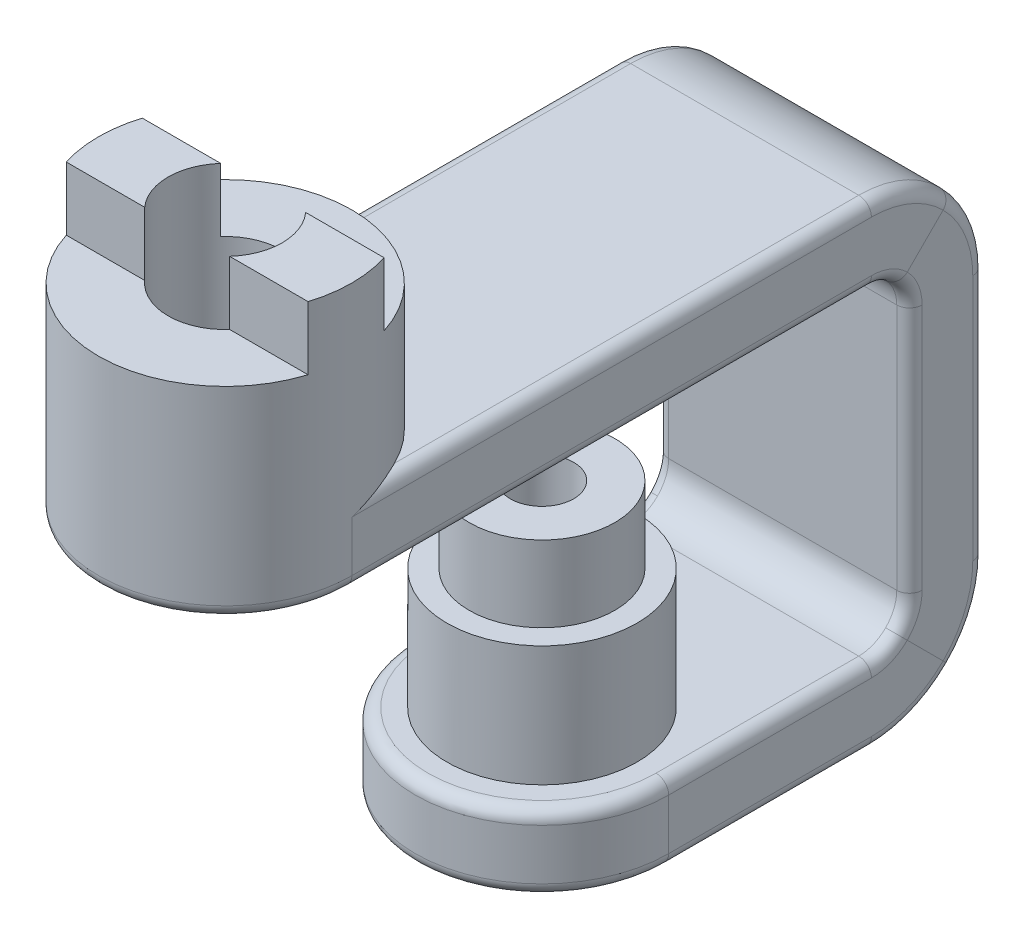
SolidWorks part; units mm, degrees
ref_plane "Front Plane" through (0, 0, 0) normal (0, 0, 1) x (1, 0, 0)
ref_plane "Top Plane" through (0, 0, 0) normal (0, 1, 0) x (1, 0, 0)
ref_plane "Right Plane" through (0, 0, 0) normal (1, 0, 0) x (0, 0, -1)
sketch "Sketch2" plane through (0, 0, 0) normal (1, 0, 0) x (0, 0, -1)
  line L0 (0, 0) -> (50, 0)
  line L1 (50, 0) -> (50, 75)
  line L2 (50, 75) -> (-50, 75)
  dimension "D1" = 75
  dimension "D2" = 50
  dimension "D3" = 100
sketch "Sketch3" plane through (0, 0, 0) normal (0, 0, 1) x (1, 0, 0)
  line L1 (-20, 12) -> (20, 12)
  line L2 (-20, 12) -> (-20, 0)
  line L3 (-20, 0) -> (20, 0)
  line L4 (20, 12) -> (20, 0)
  point P4 (0, 0)
  dimension "D1" = 12
  dimension "D2" = 40
sweep "Sweep1" add profiles "Sketch3" path "Sketch2"
sketch "Sketch4" plane through (0, 12, 0) normal (0, 1, 0) x (1, 0, 0)
  line L0 (20, 0) -> (-20, 0) construction
  line L1 (-20, 0) -> (20, 0)
  arc A0 (-20, 0) -> (20, 0) centre (0, 0) ccw
extrude "Boss-Extrude1" add sketch "Sketch4" against normal up to surface (12 mm away) up to face at (0, 0, -25)
sketch "Sketch5" plane through (0, 75, 0) normal (0, 1, 0) x (1, 0, 0)
  line L0 (-20, -50) -> (20, -50) construction
  circle A0 centre (0, -50) radius 20
extrude "Boss-Extrude2" add sketch "Sketch5" along normal blind 20 and the other way up to surface (12 mm away) other way up to face at (0, 63, 6)
sketch "Sketch7" plane through (0, 12, 0) normal (0, 1, 0) x (1, 0, 0)
  circle A0 centre (0, 0) radius 11.5
  dimension "D1" = 23
extrude "Boss-Extrude4" add sketch "Sketch7" along normal blind 31
sketch "Sketch8" plane through (0, 12, 0) normal (0, 1, 0) x (1, 0, 0)
  circle A0 centre (0, 0) radius 15
  dimension "D1" = 30
extrude "Boss-Extrude5" add sketch "Sketch8" along normal blind 19
sketch "Sketch9" plane through (0, 95, 0) normal (0, 1, 0) x (1, 0, 0)
  circle A0 centre (0, -50) radius 9
  dimension "D1" = 18
extrude "Cut-Extrude1" cut sketch "Sketch9" against normal up to surface (32 mm away) up to face at (0, 63, 11)
sketch "Sketch10" plane through (0, 95, 0) normal (0, 1, 0) x (1, 0, 0)
  line L0 (-20, -50) -> (-9, -50) construction
  line L1 (-19.0788, -44) -> (-6.7082, -44)
  line L2 (-19.0788, -56) -> (-6.7082, -56)
  line L3 (6.7082, -44) -> (19.0788, -44)
  line L4 (9, -50) -> (20, -50) construction
  line L5 (6.7082, -56) -> (19.0788, -56)
  circle A0 centre (0, -50) radius 20 construction
  arc A1 (20, -50) -> (-20, -50) centre (0, -50) ccw construction
  arc A2 (-6.7082, -44) -> (-6.7082, -56) centre (0, -50) ccw
  arc A3 (6.7082, -56) -> (6.7082, -44) centre (0, -50) ccw
  circle A4 centre (0, -50) radius 9 construction
  arc A5 (-19.0788, -44) -> (-19.0788, -56) centre (0, -50) ccw
  arc A6 (19.0788, -56) -> (19.0788, -44) centre (0, -50) ccw
  dimension "D3" = 9
  dimension "D1" = 12
  dimension "D2" = 6
extrude "Boss-Extrude6" add sketch "Sketch10" along normal blind 10
hole_wizard "CBORE for M8 Hex Head Bolt1" positions "Sketch11" profile "Sketch12" counterbore size "M8" standard "ANSI Metric"
sketch "Sketch11" plane through (0, 0, 0) normal (0, -1, 0) x (-1, 0, 0)
  point P0 (0, 0)
sketch "Sketch12" plane through (0, 0, 0) normal (1, 0, 0) x (0, 0, -1)
  line L0 (0, 0) -> (0, 46.0043)
  line L1 (0, 46.0043) -> (5, 43)
  line L2 (5, 43) -> (5, 5.68)
  line L3 (5, 5.68) -> (9.005, 5.68)
  line L4 (9.005, 5.68) -> (9.005, 0)
  line L5 (9.005, 0) -> (0, 0)
  line L10 (0, 46.0043) -> (-5, 43) construction
  line L11 (0, -6.35) -> (0, 107.95) construction
  dimension "Hole Dia." = 10
  dimension "Hole Depth" = 43
  dimension "C'Bore Dia." = 18.01
  dimension "C'Bore Depth" = 5.68
  dimension "Drill Angle" = 118
fillet "Fillet2" radius 18 2 edges at (0, 0, -50) (0, 75, -50)
fillet "Fillet3" radius 2 15 edges at (-20, 75, 9) (-20, 73.6298, -38.8883) (-20, 63.8883, -48.6298) (-20, 37.5, -50) (-20, 11.1117, -48.6298) (-20, 1.3702, -38.8883) (-20, 0, -16) (0, 0, 20) (20, 0, -16) (20, 1.3702, -38.8883) (20, 11.1117, -48.6298) (20, 37.5, -50) (20, 63.8883, -48.6298) (20, 73.6298, -38.8883) (20, 75, 9)
fillet "Fillet4" radius 6 2 edges at (0, 12, -38) (0, 63, -38)
fillet "Fillet5" radius 2 16 edges at (-20, 63, 9) (0, 63, 70) (-20, 37.5, -38) (-20, 15.7039, -37.5433) (-20, 12.4567, -34.2961) (-20, 12, -16) (0, 12, 20) (20, 37.5, -38) (20, 15.7039, -37.5433) (20, 12.4567, -34.2961) (20, 63, 9) (20, 12, -16) (-20, 59.2961, -37.5433) (-20, 62.5433, -34.2961) (20, 62.5433, -34.2961) (20, 59.2961, -37.5433)
